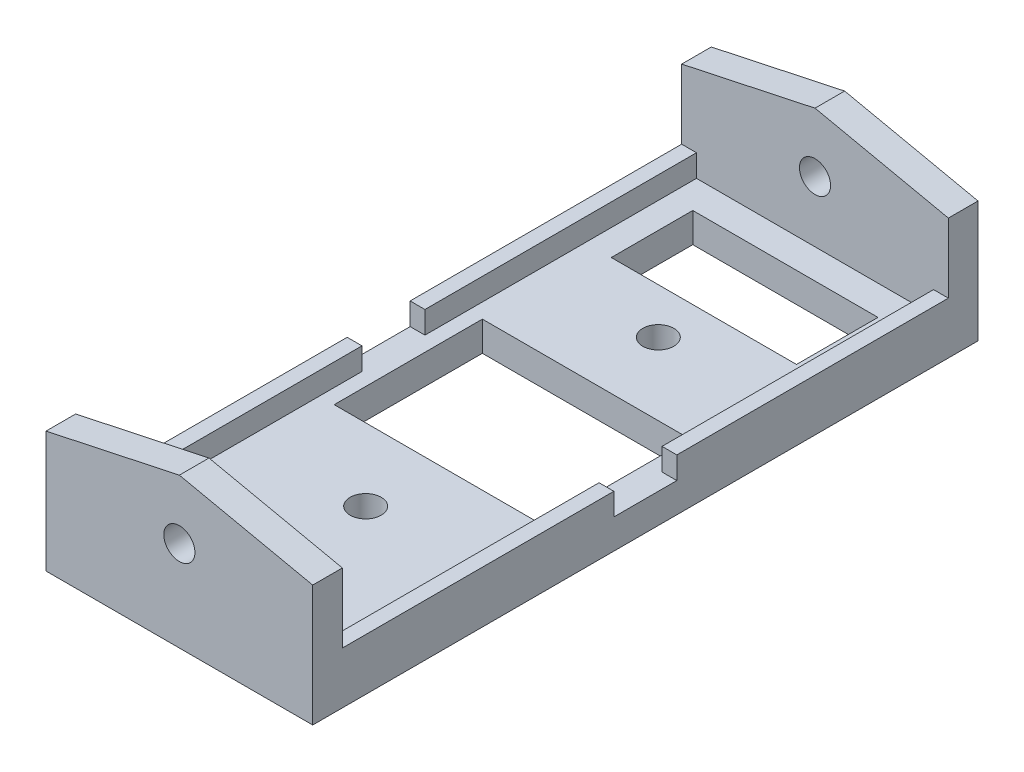
SolidWorks part; units mm, degrees
ref_plane "Front Plane" through (0, 0, 0) normal (0, 0, 1) x (1, 0, 0)
ref_plane "Top Plane" through (0, 0, 0) normal (0, 1, 0) x (1, 0, 0)
ref_plane "Right Plane" through (0, 0, 0) normal (1, 0, 0) x (0, 0, -1)
sketch "Sketch1" plane through (0, 0, 0) normal (0, 0, 1) x (1, 0, 0)
  line L2 (-40.4, 110) -> (0, 118.6383) construction
  line L3 (-18, 114.7896) -> (0, 114.7896)
  line L4 (0, 114.7896) -> (18, 114.7896)
  line L5 (0, 118.6383) -> (40.4, 110) construction
  line L11 (18, 114.7896) -> (18, 121.7896)
  line L12 (18, 121.7896) -> (16, 121.7896)
  line L13 (16, 121.7896) -> (16, 118.7896)
  line L14 (16, 118.7896) -> (-16, 118.7896)
  line L15 (-16, 118.7896) -> (-16, 121.7896)
  line L16 (-16, 121.7896) -> (-18, 121.7896)
  line L17 (-18, 121.7896) -> (-18, 114.7896)
  point P0 (6.1994, 121.9253)
  point P15 (0, 118.7896)
  dimension "D1" = 32
  dimension "D2" = 2
  dimension "D3" = 3
  dimension "D4" = 4
extrude "Boss-Extrude1" add sketch "Sketch1" along normal up to surface (89.8 mm away)
sketch "Sketch2" plane through (0, 114.7896, 0) normal (0, -1, 0) x (1, 0, 0)
  line L0 (18, 89.8) -> (18, 0) construction
  line L5 (-14, 54.9) -> (14, 54.9)
  line L6 (-14, 54.9) -> (-14, 34.9)
  line L7 (-14, 34.9) -> (14, 34.9)
  line L8 (14, 54.9) -> (14, 34.9)
  point P4 (0, 34.9)
  point P8 (18, 44.9)
  point P9 (14, 44.9)
  point P10 (10.8798, 33.7195)
  dimension "D1" = 4
  dimension "D2" = 20
extrude "Cut-Extrude1" cut sketch "Sketch2" against normal up to next
sketch "Sketch3" plane through (-18, 0, 0) normal (-1, 0, 0) x (0, 0, 1)
  line L0 (89.8, 121.7896) -> (0, 121.7896) construction
  line L1 (40.65, 118.7896) -> (49.15, 118.7896)
  line L2 (40.65, 118.7896) -> (40.65, 121.7896)
  line L3 (40.65, 121.7896) -> (49.15, 121.7896)
  line L4 (49.15, 118.7896) -> (49.15, 121.7896)
  line L5 (89.8, 118.7896) -> (0, 118.7896) construction
  point P6 (0, 0)
  point P9 (44.9, 121.7896)
  point P10 (44.9, 121.7896)
  dimension "D1" = 8.5
extrude "Cut-Extrude2" cut sketch "Sketch3" against normal through all
sketch "Sketch4" plane through (0, 118.7896, 0) normal (0, 1, 0) x (1, 0, 0)
  circle A0 centre (0, -25.15) radius 2.1 construction
  circle A1 centre (0, -64.65) radius 2.1 construction
  circle A2 centre (0, -25.15) radius 2.1
  circle A3 centre (0, -64.65) radius 2.1
extrude "Cut-Extrude3" cut sketch "Sketch4" against normal through all
ref_plane "Plane2" through (0, 0, 44.9) normal (0, 0, -1) x (-1, 0, 0)
sketch "Sketch5" plane through (0, 0, 0) normal (0, 0, 1) x (1, 0, 0)
  line L0 (-18, 114.7896) -> (-18, 131.1512)
  line L1 (-56.4, 122.9405) -> (0, 135) construction
  line L2 (-18, 131.1512) -> (0, 135)
  line L3 (0, 135) -> (18, 131.1512)
  line L4 (0, 135) -> (56.4, 122.9405) construction
  line L5 (18, 131.1512) -> (18, 114.7896)
  line L6 (18, 114.7896) -> (-18, 114.7896)
  line L7 (0.6273, 134.8659) -> (54.0273, 123.4479) construction
  line L8 (-54.0273, 123.4479) -> (-0.6273, 134.8659) construction
  circle A0 centre (0, 127) radius 2.1
  point P7 (0.3403, 135.5527)
  point P14 (0, 0)
  point P15 (0.7709, 135.701)
  dimension "D1" = 4.2
  dimension "D2" = 8
extrude "Boss-Extrude2" add sketch "Sketch5" along normal blind 4
mirror "Mirror1" about plane through (0, 0, 44.9) normal (0, 0, -1) of "Boss-Extrude2"
sketch "Sketch6" plane through (0, 118.7896, 0) normal (0, 1, 0) x (1, 0, 0)
  line L1 (12.5, -19) -> (-12.5, -19)
  line L2 (12.5, -19) -> (12.5, -8)
  line L3 (12.5, -8) -> (-12.5, -8)
  line L4 (-12.5, -19) -> (-12.5, -8)
  point P4 (0, -8)
  dimension "D1" = 11
  dimension "D2" = 25
  dimension "D3" = 8
extrude "Cut-Extrude4" cut sketch "Sketch6" against normal through all
equation "\"width\"= 24"
equation "\"thk\"= 3"
equation "\"holesize\"= 4.2"
equation "\"holedistance\"= ( 20 + 12 ) / 2"
equation "\"threaded_hole\"= 3.9"
equation "\"fillet_radius\"= 2"
equation "\"ground_clearance\"= 25"
equation "\"tire_thk\"= 3"
equation "\"innerwheel_diam\" = \"wheel_diam\"-2*\"tire_thk\""
equation "\"innerwheel_thk\"= 8"
equation "\"wheel_diam\"= 2*(\"width\"/2+\"ground_clearance\")"
equation "\"coloursensor_holesize\"= 2.65"
equation "\"hole_to_edge\" = 4"
equation "\"D1@Sketch5\"=\"holesize\""
